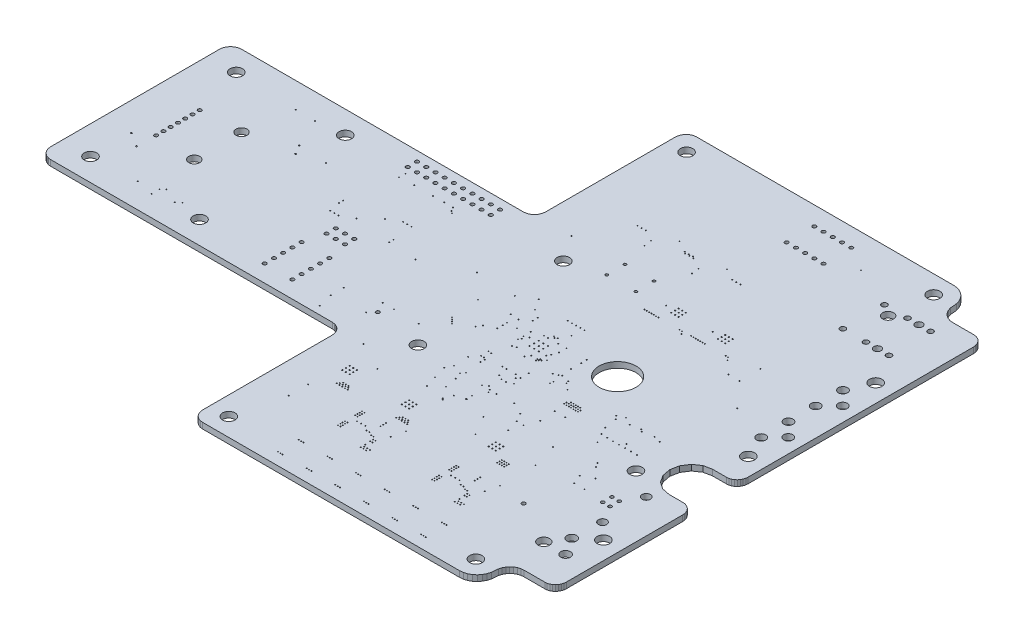
SolidWorks part; units mm, degrees
ref_plane "Front Plane" through (0, 0, 0) normal (0, 0, 1) x (1, 0, 0)
ref_plane "Top Plane" through (0, 0, 0) normal (0, 1, 0) x (1, 0, 0)
ref_plane "Right Plane" through (0, 0, 0) normal (1, 0, 0) x (0, 0, -1)
ref_plane "Dielectric_Layer Layer 1" through (0, 1.6, 0) normal (0, 1, 0) x (1, 0, 0)
sketch "Sketch1" plane through (0, 0, 0) normal (0, 1, 0) x (1, 0, 0)
  line L0 (90.797, -59) -> (91.3624, -58.9424)
  line L1 (91.3624, -58.9424) -> (91.906, -58.7716)
  line L2 (91.906, -58.7716) -> (92.4069, -58.4944)
  line L3 (92.4069, -58.4944) -> (92.8461, -58.1213)
  line L4 (92.8461, -58.1213) -> (93.2064, -57.6667)
  line L5 (93.2064, -57.6667) -> (93.4742, -57.148)
  line L6 (93.4742, -57.148) -> (93.6391, -56.5853)
  line L7 (93.6391, -56.5853) -> (93.6948, -56)
  line L8 (93.6948, -56) -> (93.6948, -24)
  line L9 (93.6948, -24) -> (93.6391, -23.4147)
  line L10 (93.6391, -23.4147) -> (93.4742, -22.8519)
  line L11 (93.4742, -22.8519) -> (93.2064, -22.3333)
  line L12 (93.2064, -22.3333) -> (92.8461, -21.8787)
  line L13 (92.8461, -21.8787) -> (92.4069, -21.5056)
  line L14 (92.4069, -21.5056) -> (91.906, -21.2284)
  line L15 (91.906, -21.2284) -> (91.3624, -21.0576)
  line L16 (91.3624, -21.0576) -> (90.797, -21)
  line L17 (90.797, -21) -> (86.9333, -21)
  line L18 (86.9333, -21) -> (84.7155, -20.5433)
  line L19 (84.7155, -20.5433) -> (82.8353, -19.2426)
  line L20 (82.8353, -19.2426) -> (81.5789, -17.2961)
  line L21 (81.5789, -17.2961) -> (81.1378, -15)
  line L22 (81.1378, -15) -> (81.5789, -12.7039)
  line L23 (81.5789, -12.7039) -> (82.8353, -10.7574)
  line L24 (82.8353, -10.7574) -> (84.7155, -9.4567)
  line L25 (84.7155, -9.4567) -> (86.9333, -9)
  line L26 (86.9333, -9) -> (90.797, -9)
  line L27 (90.797, -9) -> (91.3624, -8.9424)
  line L28 (91.3624, -8.9424) -> (91.906, -8.7716)
  line L29 (91.906, -8.7716) -> (92.4069, -8.4944)
  line L30 (92.4069, -8.4944) -> (92.8461, -8.1213)
  line L31 (92.8461, -8.1213) -> (93.2064, -7.6667)
  line L32 (93.2064, -7.6667) -> (93.4742, -7.148)
  line L33 (93.4742, -7.148) -> (93.6391, -6.5853)
  line L34 (93.6391, -6.5853) -> (93.6948, -6)
  line L35 (93.6948, -6) -> (93.6948, 56)
  line L36 (93.6948, 56) -> (93.6391, 56.5853)
  line L37 (93.6391, 56.5853) -> (93.4742, 57.148)
  line L38 (93.4742, 57.148) -> (93.2064, 57.6667)
  line L39 (93.2064, 57.6667) -> (92.8461, 58.1213)
  line L40 (92.8461, 58.1213) -> (92.4069, 58.4944)
  line L41 (92.4069, 58.4944) -> (91.906, 58.7716)
  line L42 (91.906, 58.7716) -> (91.3624, 58.9424)
  line L43 (91.3624, 58.9424) -> (90.797, 59)
  line L44 (90.797, 59) -> (85.0015, 59)
  line L45 (85.0015, 59) -> (84.2477, 59.0769)
  line L46 (84.2477, 59.0769) -> (83.5229, 59.3045)
  line L47 (83.5229, 59.3045) -> (82.8549, 59.6741)
  line L48 (82.8549, 59.6741) -> (82.2694, 60.1716)
  line L49 (82.2694, 60.1716) -> (81.7889, 60.7777)
  line L50 (81.7889, 60.7777) -> (81.4319, 61.4693)
  line L51 (81.4319, 61.4693) -> (81.212, 62.2196)
  line L52 (81.212, 62.2196) -> (81.1378, 63)
  line L53 (81.1378, 63) -> (81.045, 63.9755)
  line L54 (81.045, 63.9755) -> (80.7701, 64.9134)
  line L55 (80.7701, 64.9134) -> (80.3238, 65.7779)
  line L56 (80.3238, 65.7779) -> (79.7232, 66.5355)
  line L57 (79.7232, 66.5355) -> (78.9913, 67.1573)
  line L58 (78.9913, 67.1573) -> (78.1564, 67.6194)
  line L59 (78.1564, 67.6194) -> (77.2503, 67.9039)
  line L60 (77.2503, 67.9039) -> (76.3081, 68)
  line L61 (76.3081, 68) -> (5.5183, 68)
  line L62 (5.5183, 68) -> (4.953, 67.9424)
  line L63 (4.953, 67.9424) -> (4.4094, 67.7716)
  line L64 (4.4094, 67.7716) -> (3.9084, 67.4944)
  line L65 (3.9084, 67.4944) -> (3.4693, 67.1213)
  line L66 (3.4693, 67.1213) -> (3.1089, 66.6667)
  line L67 (3.1089, 66.6667) -> (2.8411, 66.148)
  line L68 (2.8411, 66.148) -> (2.6762, 65.5853)
  line L69 (2.6762, 65.5853) -> (2.6206, 65)
  line L70 (2.6206, 65) -> (2.6206, 29.337)
  line L71 (2.6206, 29.337) -> (2.5167, 28.5481)
  line L72 (2.5167, 28.5481) -> (2.2122, 27.813)
  line L73 (2.2122, 27.813) -> (1.7278, 27.1817)
  line L74 (1.7278, 27.1817) -> (1.0965, 26.6974)
  line L75 (1.0965, 26.6974) -> (0.3614, 26.3929)
  line L76 (0.3614, 26.3929) -> (-0.4274, 26.289)
  line L77 (-0.4274, 26.289) -> (-77.978, 26.289)
  line L78 (-77.978, 26.289) -> (-78.7669, 26.1851)
  line L79 (-78.7669, 26.1851) -> (-79.502, 25.8806)
  line L80 (-79.502, 25.8806) -> (-80.1333, 25.3963)
  line L81 (-80.1333, 25.3963) -> (-80.6176, 24.765)
  line L82 (-80.6176, 24.765) -> (-80.9221, 24.0299)
  line L83 (-80.9221, 24.0299) -> (-81.026, 23.241)
  line L84 (-81.026, 23.241) -> (-81.026, -23.241)
  line L85 (-81.026, -23.241) -> (-80.9221, -24.0299)
  line L86 (-80.9221, -24.0299) -> (-80.6176, -24.765)
  line L87 (-80.6176, -24.765) -> (-80.1333, -25.3963)
  line L88 (-80.1333, -25.3963) -> (-79.502, -25.8806)
  line L89 (-79.502, -25.8806) -> (-78.7669, -26.1851)
  line L90 (-78.7669, -26.1851) -> (-77.978, -26.289)
  line L91 (-77.978, -26.289) -> (-0.4274, -26.289)
  line L92 (-0.4274, -26.289) -> (0.3614, -26.3929)
  line L93 (0.3614, -26.3929) -> (1.0965, -26.6974)
  line L94 (1.0965, -26.6974) -> (1.7278, -27.1817)
  line L95 (1.7278, -27.1817) -> (2.2122, -27.813)
  line L96 (2.2122, -27.813) -> (2.5167, -28.5481)
  line L97 (2.5167, -28.5481) -> (2.6206, -29.337)
  line L98 (2.6206, -29.337) -> (2.6206, -65)
  line L99 (2.6206, -65) -> (2.6762, -65.5853)
  line L100 (2.6762, -65.5853) -> (2.8411, -66.148)
  line L101 (2.8411, -66.148) -> (3.1089, -66.6667)
  line L102 (3.1089, -66.6667) -> (3.4693, -67.1213)
  line L103 (3.4693, -67.1213) -> (3.9084, -67.4944)
  line L104 (3.9084, -67.4944) -> (4.4094, -67.7716)
  line L105 (4.4094, -67.7716) -> (4.953, -67.9424)
  line L106 (4.953, -67.9424) -> (5.5183, -68)
  line L107 (5.5183, -68) -> (76.3081, -68)
  line L108 (76.3081, -68) -> (77.2503, -67.9039)
  line L109 (77.2503, -67.9039) -> (78.1564, -67.6194)
  line L110 (78.1564, -67.6194) -> (78.9913, -67.1573)
  line L111 (78.9913, -67.1573) -> (79.7232, -66.5355)
  line L112 (79.7232, -66.5355) -> (80.3238, -65.7779)
  line L113 (80.3238, -65.7779) -> (80.7701, -64.9134)
  line L114 (80.7701, -64.9134) -> (81.045, -63.9755)
  line L115 (81.045, -63.9755) -> (81.1378, -63)
  line L116 (81.1378, -63) -> (81.212, -62.2196)
  line L117 (81.212, -62.2196) -> (81.4319, -61.4693)
  line L118 (81.4319, -61.4693) -> (81.7889, -60.7777)
  line L119 (81.7889, -60.7777) -> (82.2694, -60.1716)
  line L120 (82.2694, -60.1716) -> (82.8549, -59.6741)
  line L121 (82.8549, -59.6741) -> (83.5229, -59.3045)
  line L122 (83.5229, -59.3045) -> (84.2477, -59.0769)
  line L123 (84.2477, -59.0769) -> (85.0015, -59)
  line L124 (85.0015, -59) -> (90.797, -59)
extrude "Board_Outline" add sketch "Sketch1" along normal blind 1.6 separate body
sketch "Sketch2" plane through (0, 0, 0) normal (0, 1, 0) x (1, 0, 0)
  circle A0 centre (51.786, 0) radius 5.08
  circle A1 centre (84.391, -36.754) radius 1.15
  circle A2 centre (84.391, -24.714) radius 1.15
  circle A3 centre (80.874, 53.839) radius 1
  circle A4 centre (80.874, 42.409) radius 1
  circle A5 centre (74.524, 51.709) radius 1.5
  circle A6 centre (29.591, -4.191) radius 0.127
  circle A7 centre (29.972, -7.239) radius 0.127
  circle A8 centre (47.244, -22.225) radius 0.127
  circle A9 centre (29.206, -3.306) radius 0.127
  circle A10 centre (29.174, -1.306) radius 0.127
  circle A11 centre (29.19, -4.806) radius 0.127
  circle A12 centre (34.163, -8.001) radius 0.127
  circle A13 centre (38.136, -5.806) radius 0.127
  circle A14 centre (37.993, -2.306) radius 0.127
  circle A15 centre (38.025, -0.306) radius 0.127
  circle A16 centre (34.417, 0.889) radius 0.127
  circle A17 centre (33.909, 0.508) radius 0.127
  circle A18 centre (33.405, 0.893) radius 0.127
  circle A19 centre (55.753, -35.814) radius 0.127
  circle A20 centre (56.388, -35.814) radius 0.127
  circle A21 centre (55.753, -36.449) radius 0.127
  circle A22 centre (56.388, -36.449) radius 0.127
  circle A23 centre (55.753, -37.084) radius 0.127
  circle A24 centre (56.388, -37.084) radius 0.127
  circle A25 centre (57.023, -37.084) radius 0.127
  circle A26 centre (57.023, -36.449) radius 0.127
  circle A27 centre (57.023, -35.814) radius 0.127
  circle A28 centre (57.658, -35.814) radius 0.127
  circle A29 centre (57.658, -36.449) radius 0.127
  circle A30 centre (57.658, -37.084) radius 0.127
  circle A31 centre (50.8, -43.434) radius 0.127
  circle A32 centre (51.435, -43.434) radius 0.127
  circle A33 centre (50.8, -44.069) radius 0.127
  circle A34 centre (51.435, -44.069) radius 0.127
  circle A35 centre (51.435, -44.704) radius 0.127
  circle A36 centre (50.8, -44.704) radius 0.127
  circle A37 centre (50.8, -45.339) radius 0.127
  circle A38 centre (51.435, -45.339) radius 0.127
  circle A39 centre (61.595, -42.164) radius 0.127
  circle A40 centre (35.687, -42.164) radius 0.127
  circle A41 centre (24.892, -43.434) radius 0.127
  circle A42 centre (25.527, -43.434) radius 0.127
  circle A43 centre (24.892, -44.069) radius 0.127
  circle A44 centre (24.892, -44.704) radius 0.127
  circle A45 centre (24.892, -45.339) radius 0.127
  circle A46 centre (25.527, -44.069) radius 0.127
  circle A47 centre (25.527, -44.704) radius 0.127
  circle A48 centre (25.527, -45.339) radius 0.127
  circle A49 centre (14.732, -40.259) radius 0.127
  circle A50 centre (15.113, -39.751) radius 0.127
  circle A51 centre (15.494, -40.259) radius 0.127
  circle A52 centre (15.875, -39.751) radius 0.127
  circle A53 centre (16.256, -40.259) radius 0.127
  circle A54 centre (16.637, -39.751) radius 0.127
  circle A55 centre (17.018, -40.259) radius 0.127
  circle A56 centre (17.399, -39.751) radius 0.127
  circle A57 centre (17.78, -40.259) radius 0.127
  circle A58 centre (17.018, -39.243) radius 0.127
  circle A59 centre (16.256, -39.243) radius 0.127
  circle A60 centre (15.494, -39.243) radius 0.127
  circle A61 centre (31.115, -40.259) radius 0.127
  circle A62 centre (31.496, -39.751) radius 0.127
  circle A63 centre (31.877, -40.259) radius 0.127
  circle A64 centre (32.258, -39.751) radius 0.127
  circle A65 centre (32.639, -40.259) radius 0.127
  circle A66 centre (33.02, -39.751) radius 0.127
  circle A67 centre (33.401, -40.259) radius 0.127
  circle A68 centre (33.782, -39.751) radius 0.127
  circle A69 centre (34.163, -40.259) radius 0.127
  circle A70 centre (33.401, -39.243) radius 0.127
  circle A71 centre (32.639, -39.243) radius 0.127
  circle A72 centre (31.877, -39.243) radius 0.127
  circle A73 centre (50.419, -24.511) radius 0.127
  circle A74 centre (48.514, -24.511) radius 0.127
  circle A75 centre (11.049, -49.784) radius 0.127
  circle A76 centre (61.087, -51.562) radius 0.127
  circle A77 centre (59.182, -50.927) radius 0.127
  circle A78 centre (59.182, -52.197) radius 0.127
  circle A79 centre (59.563, -51.562) radius 0.127
  circle A80 centre (59.944, -52.197) radius 0.127
  circle A81 centre (60.325, -51.562) radius 0.127
  circle A82 centre (60.706, -52.197) radius 0.127
  circle A83 centre (63.627, -58.928) radius 0.127
  circle A84 centre (62.992, -58.928) radius 0.127
  circle A85 centre (62.357, -58.928) radius 0.127
  circle A86 centre (55.753, -58.928) radius 0.127
  circle A87 centre (55.118, -58.928) radius 0.127
  circle A88 centre (54.483, -58.928) radius 0.127
  circle A89 centre (47.879, -58.928) radius 0.127
  circle A90 centre (47.244, -58.928) radius 0.127
  circle A91 centre (46.609, -58.928) radius 0.127
  circle A92 centre (40.005, -58.928) radius 0.127
  circle A93 centre (39.37, -58.928) radius 0.127
  circle A94 centre (38.735, -58.928) radius 0.127
  circle A95 centre (32.131, -58.928) radius 0.127
  circle A96 centre (31.496, -58.928) radius 0.127
  circle A97 centre (30.861, -58.928) radius 0.127
  circle A98 centre (24.257, -58.928) radius 0.127
  circle A99 centre (23.622, -58.928) radius 0.127
  circle A100 centre (22.987, -58.928) radius 0.127
  circle A101 centre (41.529, 23.622) radius 0.127
  circle A102 centre (39.497, 19.685) radius 0.127
  circle A103 centre (40.132, 19.685) radius 0.127
  circle A104 centre (40.767, 19.685) radius 0.127
  circle A105 centre (41.402, 19.685) radius 0.127
  circle A106 centre (42.037, 19.685) radius 0.127
  circle A107 centre (42.672, 19.685) radius 0.127
  circle A108 centre (43.307, 19.685) radius 0.127
  circle A109 centre (52.197, 19.812) radius 0.127
  circle A110 centre (52.832, 19.812) radius 0.127
  circle A111 centre (53.467, 19.812) radius 0.127
  circle A112 centre (54.102, 19.812) radius 0.127
  circle A113 centre (54.737, 19.812) radius 0.127
  circle A114 centre (55.372, 19.812) radius 0.127
  circle A115 centre (56.007, 19.812) radius 0.127
  circle A116 centre (35.179, -51.562) radius 0.127
  circle A117 centre (33.274, -50.927) radius 0.127
  circle A118 centre (33.274, -52.197) radius 0.127
  circle A119 centre (33.655, -51.562) radius 0.127
  circle A120 centre (34.036, -52.197) radius 0.127
  circle A121 centre (34.417, -51.562) radius 0.127
  circle A122 centre (34.798, -52.197) radius 0.127
  circle A123 centre (-50.8, 19.304) radius 0.127
  circle A124 centre (54.229, 23.749) radius 0.127
  circle A125 centre (-47.117, 11.303) radius 0.1905
  circle A126 centre (-69.342, -11.303) radius 0.1905
  circle A127 centre (57.658, -47.879) radius 0.127
  circle A128 centre (58.293, -47.879) radius 0.127
  circle A129 centre (56.769, -47.371) radius 0.127
  circle A130 centre (56.007, -47.371) radius 0.127
  circle A131 centre (54.737, -46.482) radius 0.127
  circle A132 centre (53.594, -46.482) radius 0.127
  circle A133 centre (52.451, -46.482) radius 0.127
  circle A134 centre (56.896, -44.45) radius 0.127
  circle A135 centre (56.896, -42.926) radius 0.127
  circle A136 centre (56.896, -43.688) radius 0.127
  circle A137 centre (30.988, -42.926) radius 0.127
  circle A138 centre (30.988, -43.688) radius 0.127
  circle A139 centre (30.988, -44.45) radius 0.127
  circle A140 centre (27.686, -46.482) radius 0.127
  circle A141 centre (26.543, -46.482) radius 0.127
  circle A142 centre (28.829, -46.482) radius 0.127
  circle A143 centre (30.099, -47.371) radius 0.127
  circle A144 centre (30.861, -47.371) radius 0.127
  circle A145 centre (31.877, -47.879) radius 0.127
  circle A146 centre (32.512, -47.879) radius 0.127
  circle A147 centre (37.465, 34.798) radius 0.127
  circle A148 centre (31.75, 38.608) radius 0.127
  circle A149 centre (32.893, 38.608) radius 0.127
  circle A150 centre (34.036, 38.608) radius 0.127
  circle A151 centre (44.45, 38.862) radius 0.127
  circle A152 centre (45.593, 38.862) radius 0.127
  circle A153 centre (46.736, 38.862) radius 0.127
  circle A154 centre (24.257, 34.925) radius 0.127
  circle A155 centre (20.828, 38.735) radius 0.127
  circle A156 centre (19.685, 38.735) radius 0.127
  circle A157 centre (18.542, 38.735) radius 0.127
  circle A158 centre (-14.605, 7.366) radius 0.127
  circle A159 centre (-13.462, 7.366) radius 0.127
  circle A160 centre (-12.319, 7.366) radius 0.127
  circle A161 centre (-27.305, 0) radius 0.127
  circle A162 centre (-26.162, 0) radius 0.127
  circle A163 centre (-25.019, 0) radius 0.127
  circle A164 centre (-27.94, 4.191) radius 0.127
  circle A165 centre (-27.94, 3.048) radius 0.127
  circle A166 centre (-11.684, 1.778) radius 0.127
  circle A167 centre (-11.684, 0.635) radius 0.127
  circle A168 centre (-7.112, -20.066) radius 0.127
  circle A169 centre (-7.112, -16.51) radius 0.127
  circle A170 centre (3.429, -17.653) radius 0.508
  circle A171 centre (33.528, 38.989) radius 0.127
  circle A172 centre (32.385, 38.989) radius 0.127
  circle A173 centre (31.242, 38.989) radius 0.127
  circle A174 centre (71.247, -31.369) radius 0.127
  circle A175 centre (43.561, -4.572) radius 0.127
  circle A176 centre (70.231, -28.829) radius 0.127
  circle A177 centre (52.832, -12.573) radius 0.127
  circle A178 centre (52.197, -12.573) radius 0.127
  circle A179 centre (53.467, -12.573) radius 0.127
  circle A180 centre (54.102, -12.573) radius 0.127
  circle A181 centre (51.562, -12.573) radius 0.127
  circle A182 centre (51.562, -13.208) radius 0.127
  circle A183 centre (52.197, -13.208) radius 0.127
  circle A184 centre (52.832, -13.208) radius 0.127
  circle A185 centre (53.467, -13.208) radius 0.127
  circle A186 centre (54.102, -13.208) radius 0.127
  circle A187 centre (54.737, -13.208) radius 0.127
  circle A188 centre (50.927, -13.208) radius 0.127
  circle A189 centre (50.927, -13.843) radius 0.127
  circle A190 centre (51.562, -13.843) radius 0.127
  circle A191 centre (52.197, -13.843) radius 0.127
  circle A192 centre (52.832, -13.843) radius 0.127
  circle A193 centre (53.467, -13.843) radius 0.127
  circle A194 centre (54.102, -13.843) radius 0.127
  circle A195 centre (54.737, -13.843) radius 0.127
  circle A196 centre (49.53, -27.813) radius 0.127
  circle A197 centre (31.623, 6.477) radius 0.127
  circle A198 centre (32.766, 6.477) radius 0.127
  circle A199 centre (33.909, 6.477) radius 0.127
  circle A200 centre (35.052, 6.477) radius 0.127
  circle A201 centre (36.195, 6.477) radius 0.127
  circle A202 centre (24.539, -0.028) radius 0.127
  circle A203 centre (23.749, -2.413) radius 0.127
  circle A204 centre (23.749, -3.556) radius 0.127
  circle A205 centre (23.749, -5.08) radius 0.127
  circle A206 centre (26.396, -2.306) radius 0.127
  circle A207 centre (28.829, -11.811) radius 0.127
  circle A208 centre (33.528, -13.462) radius 0.127
  circle A209 centre (34.671, -13.462) radius 0.127
  circle A210 centre (-54.925, -17.465) radius 0.127
  circle A211 centre (-50.734, -19.365) radius 0.127
  circle A212 centre (24.483, 4.544) radius 0.127
  circle A213 centre (69.088, -43.18) radius 0.508
  circle A214 centre (22.987, -64.643) radius 0.127
  circle A215 centre (23.622, -64.643) radius 0.127
  circle A216 centre (24.257, -64.643) radius 0.127
  circle A217 centre (30.861, -64.643) radius 0.127
  circle A218 centre (31.496, -64.643) radius 0.127
  circle A219 centre (32.131, -64.643) radius 0.127
  circle A220 centre (38.735, -64.643) radius 0.127
  circle A221 centre (39.37, -64.643) radius 0.127
  circle A222 centre (40.005, -64.643) radius 0.127
  circle A223 centre (46.609, -64.643) radius 0.127
  circle A224 centre (47.244, -64.643) radius 0.127
  circle A225 centre (47.879, -64.643) radius 0.127
  circle A226 centre (54.483, -64.643) radius 0.127
  circle A227 centre (55.118, -64.643) radius 0.127
  circle A228 centre (55.753, -64.643) radius 0.127
  circle A229 centre (62.357, -64.643) radius 0.127
  circle A230 centre (62.992, -64.643) radius 0.127
  circle A231 centre (63.627, -64.643) radius 0.127
  circle A232 centre (64.897, -16.002) radius 0.127
  circle A233 centre (66.548, -16.002) radius 0.127
  circle A234 centre (68.199, -16.002) radius 0.127
  circle A235 centre (69.85, -16.002) radius 0.127
  circle A236 centre (71.501, -16.002) radius 0.127
  circle A237 centre (73.152, -16.002) radius 0.127
  circle A238 centre (63.246, -15.875) radius 0.127
  circle A239 centre (29.972, -22.733) radius 0.127
  circle A240 centre (25.781, -21.717) radius 0.127
  circle A241 centre (29.972, -19.939) radius 0.127
  circle A242 centre (37.211, -13.462) radius 0.127
  circle A243 centre (36.449, -16.637) radius 0.127
  circle A244 centre (37.719, -16.637) radius 0.127
  circle A245 centre (39.243, -16.002) radius 0.127
  circle A246 centre (35.179, -16.002) radius 0.127
  circle A247 centre (35.179, -20.701) radius 0.127
  circle A248 centre (37.338, -20.701) radius 0.127
  circle A249 centre (37.719, -21.463) radius 0.127
  circle A250 centre (39.243, -20.828) radius 0.127
  circle A251 centre (21.082, -6.35) radius 0.127
  circle A252 centre (20.32, -7.62) radius 0.127
  circle A253 centre (22.225, 0.127) radius 0.127
  circle A254 centre (43.307, -7.747) radius 0.127
  circle A255 centre (43.942, -7.366) radius 0.127
  circle A256 centre (43.561, -0.254) radius 0.127
  circle A257 centre (43.561, -1.778) radius 0.127
  circle A258 centre (-56.134, 19.304) radius 0.127
  circle A259 centre (11.049, -44.45) radius 0.127
  circle A260 centre (42.926, -28.067) radius 0.127
  circle A261 centre (9.017, -27.178) radius 0.127
  circle A262 centre (26.797, -25.273) radius 0.127
  circle A263 centre (66.548, 15.748) radius 0.127
  circle A264 centre (69.596, 15.748) radius 0.127
  circle A265 centre (61.595, -32.385) radius 0.127
  circle A266 centre (14.224, -0.889) radius 0.127
  circle A267 centre (18.415, 5.08) radius 0.127
  circle A268 centre (75.819, 8.89) radius 0.127
  circle A269 centre (59.944, 58.801) radius 0.127
  circle A270 centre (74.041, -31.369) radius 0.127
  circle A271 centre (-73.152, -8.89) radius 0.1905
  circle A272 centre (-45.593, 8.763) radius 0.1905
  circle A273 centre (42.164, -8.255) radius 0.127
  circle A274 centre (11.811, -14.732) radius 0.127
  circle A275 centre (46.355, -8.636) radius 0.127
  circle A276 centre (60.96, -9.525) radius 0.127
  circle A277 centre (1.905, -19.304) radius 0.127
  circle A278 centre (16.891, -31.242) radius 0.127
  circle A279 centre (71.247, -9.271) radius 0.127
  circle A280 centre (67.564, -9.271) radius 0.127
  circle A281 centre (70.358, -24.511) radius 0.127
  circle A282 centre (51.689, -21.209) radius 0.127
  circle A283 centre (30.341, -2.806) radius 0.127
  circle A284 centre (30.905, -6.858) radius 0.127
  circle A285 centre (34.889, -6.858) radius 0.127
  circle A286 centre (36.937, -4.806) radius 0.127
  circle A287 centre (35.762, -0.329) radius 0.127
  circle A288 centre (31.905, -0.353) radius 0.127
  circle A289 centre (43.942, -20.574) radius 0.127
  circle A290 centre (51.336, -16.863) radius 0.127
  circle A291 centre (37.084, -6.985) radius 0.127
  circle A292 centre (36.576, -6.858) radius 0.127
  circle A293 centre (36.957, -6.477) radius 0.127
  circle A294 centre (37.465, -6.604) radius 0.127
  circle A295 centre (36.703, -7.366) radius 0.127
  circle A296 centre (26.67, -19.939) radius 0.127
  circle A297 centre (33.782, -27.051) radius 0.127
  circle A298 centre (36.322, -19.939) radius 0.127
  circle A299 centre (36.322, -26.162) radius 0.1905
  circle A300 centre (36.322, -24.638) radius 0.127
  circle A301 centre (32.893, -29.21) radius 0.127
  circle A302 centre (33.274, -29.591) radius 0.127
  circle A303 centre (30.607, -26.035) radius 0.127
  circle A304 centre (1.905, -14.732) radius 0.127
  circle A305 centre (4.953, -14.732) radius 0.127
  circle A306 centre (59.69, -25.654) radius 0.127
  circle A307 centre (54.272, -16.863) radius 0.127
  circle A308 centre (73.152, -9.779) radius 0.127
  circle A309 centre (61.722, -10.414) radius 0.127
  circle A310 centre (69.088, -14.859) radius 0.127
  circle A311 centre (69.596, -23.368) radius 0.127
  circle A312 centre (44.069, -10.922) radius 0.127
  circle A313 centre (38.1, -14.351) radius 0.127
  circle A314 centre (44.196, -10.033) radius 0.127
  circle A315 centre (38.735, -13.716) radius 0.127
  circle A316 centre (33.02, -0.381) radius 0.127
  circle A317 centre (27.94, -11.684) radius 0.127
  circle A318 centre (26.543, -15.875) radius 0.127
  circle A319 centre (29.276, -20.889) radius 0.127
  circle A320 centre (26.797, 1.651) radius 0.127
  circle A321 centre (26.797, 3.048) radius 0.127
  circle A322 centre (35.687, 3.429) radius 0.127
  circle A323 centre (7.62, 5.461) radius 0.127
  circle A324 centre (-3.937, 0.127) radius 0.127
  circle A325 centre (-49.53, -18.415) radius 0.127
  circle A326 centre (46.101, -7.874) radius 0.127
  circle A327 centre (48.006, -10.033) radius 0.127
  circle A328 centre (-6.096, -24.13) radius 0.127
  circle A329 centre (-55.88, -20.574) radius 0.127
  circle A330 centre (-55.88, -18.415) radius 0.127
  circle A331 centre (62.738, -8.636) radius 0.127
  circle A332 centre (28.829, -13.843) radius 0.127
  circle A333 centre (-13.589, 17.653) radius 0.127
  circle A334 centre (28.067, -13.843) radius 0.127
  circle A335 centre (29.464, -14.224) radius 0.127
  circle A336 centre (-16.637, 17.653) radius 0.127
  circle A337 centre (29.464, -15.367) radius 0.127
  circle A338 centre (-21.844, 17.653) radius 0.127
  circle A339 centre (68.199, -9.779) radius 0.127
  circle A340 centre (62.23, -13.843) radius 0.127
  circle A341 centre (14.859, -8.636) radius 0.127
  circle A342 centre (-9.906, 16.129) radius 0.127
  circle A343 centre (-25.781, 17.399) radius 0.127
  circle A344 centre (15.367, -9.144) radius 0.127
  circle A345 centre (-10.541, 16.637) radius 0.127
  circle A346 centre (-25.781, 19.177) radius 0.127
  circle A347 centre (15.875, -9.652) radius 0.127
  circle A348 centre (-11.176, 17.653) radius 0.127
  circle A349 centre (16.383, -10.16) radius 0.127
  circle A350 centre (33.147, -48.641) radius 0.127
  circle A351 centre (33.147, -49.403) radius 0.127
  circle A352 centre (33.782, -49.403) radius 0.127
  circle A353 centre (33.782, -48.641) radius 0.127
  circle A354 centre (34.925, -45.593) radius 0.127
  circle A355 centre (24.892, -48.133) radius 0.127
  circle A356 centre (25.527, -48.133) radius 0.127
  circle A357 centre (25.527, -48.768) radius 0.127
  circle A358 centre (25.527, -49.403) radius 0.127
  circle A359 centre (25.527, -50.038) radius 0.127
  circle A360 centre (24.892, -50.038) radius 0.127
  circle A361 centre (24.892, -49.403) radius 0.127
  circle A362 centre (24.892, -48.768) radius 0.127
  circle A363 centre (59.055, -48.641) radius 0.127
  circle A364 centre (59.69, -48.641) radius 0.127
  circle A365 centre (59.055, -49.403) radius 0.127
  circle A366 centre (59.69, -49.403) radius 0.127
  circle A367 centre (60.833, -45.593) radius 0.127
  circle A368 centre (50.8, -50.038) radius 0.127
  circle A369 centre (51.435, -50.038) radius 0.127
  circle A370 centre (50.8, -49.403) radius 0.127
  circle A371 centre (51.435, -49.403) radius 0.127
  circle A372 centre (51.435, -48.768) radius 0.127
  circle A373 centre (50.8, -48.768) radius 0.127
  circle A374 centre (50.8, -48.133) radius 0.127
  circle A375 centre (51.435, -48.133) radius 0.127
  circle A376 centre (11.938, 27.178) radius 0.127
  circle A377 centre (-60.833, -19.431) radius 0.127
  circle A378 centre (-39.243, 10.795) radius 0.127
  circle A379 centre (-73.223, 20.066) radius 1.7145
  circle A380 centre (-43.223, 20.066) radius 1.7145
  circle A381 centre (-73.223, -20.066) radius 1.7145
  circle A382 centre (-43.223, -20.066) radius 1.7145
  circle A383 centre (16.773, 20.066) radius 1.7145
  circle A384 centre (16.773, -19.939) radius 1.7145
  circle A385 centre (7.773, -62.992) radius 1.7145
  circle A386 centre (75.773, -62.992) radius 1.7145
  circle A387 centre (76.773, -19.939) radius 1.7145
  circle A388 centre (7.773, 62.992) radius 1.7145
  circle A389 centre (75.773, 62.992) radius 1.7145
  circle A390 centre (88.773, 34.036) radius 1.7145
  circle A391 centre (88.773, -1.016) radius 1.7145
  circle A392 centre (22.479, 7.62) radius 0.127
  circle A393 centre (88.773, -40.894) radius 1.7145
  circle A394 centre (45.974, -33.274) radius 0.127
  circle A395 centre (27.813, -28.448) radius 0.127
  circle A396 centre (64.643, -18.415) radius 0.127
  circle A397 centre (38.735, -11.43) radius 0.127
  circle A398 centre (64.897, -9.779) radius 0.127
  circle A399 centre (37.465, -3.937) radius 0.127
  circle A400 centre (73.025, -27.305) radius 0.127
  circle A401 centre (49.149, 19.685) radius 0.127
  circle A402 centre (50.419, 18.923) radius 0.127
  circle A403 centre (37.211, 36.83) radius 0.127
  circle A404 centre (24.003, 36.957) radius 0.127
  circle A405 centre (-17.78, 5.588) radius 0.127
  circle A406 centre (49.784, 19.685) radius 0.127
  circle A407 centre (69.596, 21.463) radius 0.127
  circle A408 centre (61.722, 19.812) radius 0.127
  circle A409 centre (62.992, 19.05) radius 0.127
  circle A410 centre (41.275, 40.64) radius 0.127
  circle A411 centre (-21.844, 1.778) radius 0.127
  circle A412 centre (62.357, 19.812) radius 0.127
  circle A413 centre (28.067, 40.767) radius 0.127
extrude "NPTH" cut sketch "Sketch2" along normal through all
sketch "Sketch3" plane through (0, 0, 0) normal (0, 1, 0) x (1, 0, 0)
  circle A0 centre (26.04, 22.77) radius 0.375
  circle A1 centre (26.04, 27.77) radius 0.375
  circle A2 centre (34.04, 22.77) radius 0.375
  circle A3 centre (34.04, 27.77) radius 0.375
  circle A4 centre (81, -49.53) radius 1.59
  circle A5 centre (87, -49.53) radius 1.335
  circle A6 centre (84, -44.83) radius 1.335
  circle A7 centre (79.68, -29.48) radius 0.46
  circle A8 centre (79.68, -31.98) radius 0.46
  circle A9 centre (81.68, -31.98) radius 0.46
  circle A10 centre (81.68, -29.48) radius 0.46
  circle A11 centre (77.72, 53.84) radius 0.75
  circle A12 centre (77.72, 42.41) radius 0.75
  circle A13 centre (84.07, 53.84) radius 0.75
  circle A14 centre (84.07, 42.41) radius 0.75
  circle A15 centre (71.37, 53.84) radius 0.75
  circle A16 centre (71.37, 42.41) radius 0.75
  circle A17 centre (86.04, 27.76) radius 1.25
  circle A18 centre (89.74, 24.01) radius 1.25
  circle A19 centre (86.04, 20.26) radius 1.25
  circle A20 centre (86.04, 12.76) radius 1.25
  circle A21 centre (89.74, 9.01) radius 1.25
  circle A22 centre (86.04, 5.26) radius 1.25
  circle A23 centre (-22.35, -5.97) radius 0.51
  circle A24 centre (-22.35, -3.43) radius 0.51
  circle A25 centre (-19.81, -5.97) radius 0.51
  circle A26 centre (-19.81, -3.43) radius 0.51
  circle A27 centre (-17.27, -5.97) radius 0.51
  circle A28 centre (-17.27, -3.43) radius 0.51
  circle A29 centre (-27.05, 21.08) radius 0.51
  circle A30 centre (-27.05, 23.62) radius 0.51
  circle A31 centre (-24.51, 21.08) radius 0.51
  circle A32 centre (-24.51, 23.62) radius 0.51
  circle A33 centre (-21.97, 21.08) radius 0.51
  circle A34 centre (-21.97, 23.62) radius 0.51
  circle A35 centre (-19.43, 21.08) radius 0.51
  circle A36 centre (-19.43, 23.62) radius 0.51
  circle A37 centre (-16.89, 21.08) radius 0.51
  circle A38 centre (-16.89, 23.62) radius 0.51
  circle A39 centre (-14.35, 21.08) radius 0.51
  circle A40 centre (-14.35, 23.62) radius 0.51
  circle A41 centre (-11.81, 21.08) radius 0.51
  circle A42 centre (-11.81, 23.62) radius 0.51
  circle A43 centre (-9.27, 21.08) radius 0.51
  circle A44 centre (-9.27, 23.62) radius 0.51
  circle A45 centre (-6.73, 21.08) radius 0.51
  circle A46 centre (-6.73, 23.62) radius 0.51
  circle A47 centre (-4.19, 21.08) radius 0.51
  circle A48 centre (-4.19, 23.62) radius 0.51
  circle A49 centre (-16.13, -21.59) radius 0.5
  circle A50 centre (-16.13, -19.05) radius 0.5
  circle A51 centre (-16.13, -16.51) radius 0.5
  circle A52 centre (-16.13, -13.97) radius 0.5
  circle A53 centre (-16.13, -11.43) radius 0.5
  circle A54 centre (-23.75, -11.43) radius 0.5
  circle A55 centre (-23.75, -13.97) radius 0.5
  circle A56 centre (-23.75, -16.51) radius 0.5
  circle A57 centre (-23.75, -19.05) radius 0.5
  circle A58 centre (-23.75, -21.59) radius 0.5
  circle A59 centre (53.21, 62.87) radius 0.5
  circle A60 centre (50.67, 62.87) radius 0.5
  circle A61 centre (48.13, 62.87) radius 0.5
  circle A62 centre (45.59, 62.87) radius 0.5
  circle A63 centre (43.05, 62.87) radius 0.5
  circle A64 centre (43.05, 55.25) radius 0.5
  circle A65 centre (45.59, 55.25) radius 0.5
  circle A66 centre (48.13, 55.25) radius 0.5
  circle A67 centre (50.67, 55.25) radius 0.5
  circle A68 centre (53.21, 55.25) radius 0.5
  circle A69 centre (32.38, -2.29) radius 0.15
  circle A70 centre (33.66, -2.29) radius 0.15
  circle A71 centre (34.93, -2.29) radius 0.15
  circle A72 centre (32.38, -3.56) radius 0.15
  circle A73 centre (33.66, -3.56) radius 0.15
  circle A74 centre (34.93, -3.56) radius 0.15
  circle A75 centre (32.38, -4.83) radius 0.15
  circle A76 centre (33.66, -4.83) radius 0.15
  circle A77 centre (34.93, -4.83) radius 0.15
  circle A78 centre (29.72, -35.31) radius 0.15
  circle A79 centre (30.72, -35.31) radius 0.15
  circle A80 centre (28.72, -35.31) radius 0.15
  circle A81 centre (28.72, -36.31) radius 0.15
  circle A82 centre (29.72, -36.31) radius 0.15
  circle A83 centre (30.72, -36.31) radius 0.15
  circle A84 centre (30.72, -34.31) radius 0.15
  circle A85 centre (29.72, -34.31) radius 0.15
  circle A86 centre (28.72, -34.31) radius 0.15
  circle A87 centre (51.69, -33.4) radius 0.15
  circle A88 centre (51.69, -34.4) radius 0.15
  circle A89 centre (51.69, -32.4) radius 0.15
  circle A90 centre (50.69, -32.4) radius 0.15
  circle A91 centre (50.69, -33.4) radius 0.15
  circle A92 centre (50.69, -34.4) radius 0.15
  circle A93 centre (52.69, -34.4) radius 0.15
  circle A94 centre (52.69, -33.4) radius 0.15
  circle A95 centre (52.69, -32.4) radius 0.15
  circle A96 centre (13.34, -35.31) radius 0.15
  circle A97 centre (14.34, -35.31) radius 0.15
  circle A98 centre (12.34, -35.31) radius 0.15
  circle A99 centre (12.34, -36.31) radius 0.15
  circle A100 centre (13.34, -36.31) radius 0.15
  circle A101 centre (14.34, -36.31) radius 0.15
  circle A102 centre (14.34, -34.31) radius 0.15
  circle A103 centre (13.34, -34.31) radius 0.15
  circle A104 centre (12.34, -34.31) radius 0.15
  circle A105 centre (44.96, 23.62) radius 0.15
  circle A106 centre (44.96, 22.62) radius 0.15
  circle A107 centre (44.96, 24.62) radius 0.15
  circle A108 centre (43.96, 24.62) radius 0.15
  circle A109 centre (43.96, 23.62) radius 0.15
  circle A110 centre (43.96, 22.62) radius 0.15
  circle A111 centre (45.96, 22.62) radius 0.15
  circle A112 centre (45.96, 23.62) radius 0.15
  circle A113 centre (45.96, 24.62) radius 0.15
  circle A114 centre (57.66, 23.75) radius 0.15
  circle A115 centre (57.66, 22.75) radius 0.15
  circle A116 centre (57.66, 24.75) radius 0.15
  circle A117 centre (56.66, 24.75) radius 0.15
  circle A118 centre (56.66, 23.75) radius 0.15
  circle A119 centre (56.66, 22.75) radius 0.15
  circle A120 centre (58.66, 22.75) radius 0.15
  circle A121 centre (58.66, 23.75) radius 0.15
  circle A122 centre (58.66, 24.75) radius 0.15
  circle A123 centre (-69.22, 6) radius 0.5
  circle A124 centre (-69.22, -6) radius 0.5
  circle A125 centre (-69.22, 0) radius 0.5
  circle A126 centre (-69.22, 4) radius 0.5
  circle A127 centre (-58.22, -6.5) radius 1.5
  circle A128 centre (-58.22, 6.5) radius 1.5
  circle A129 centre (-69.22, -4) radius 0.5
  circle A130 centre (-69.22, -2) radius 0.5
  circle A131 centre (-69.22, 2) radius 0.5
extrude "PTH" cut sketch "Sketch3" along normal through all
